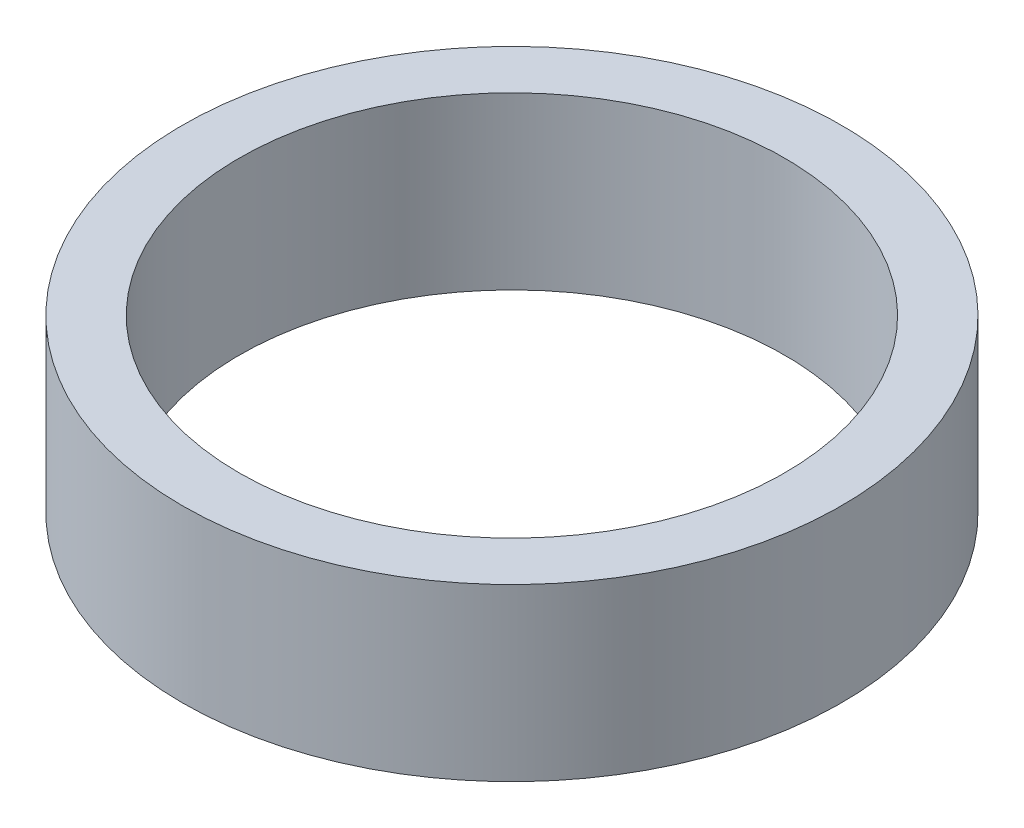
SolidWorks part; units mm, degrees
material "Teak"
ref_plane "Front Plane" through (0, 0, 0) normal (0, 0, 1) x (1, 0, 0)
ref_plane "Top Plane" through (0, 0, 0) normal (0, 1, 0) x (1, 0, 0)
ref_plane "Right Plane" through (0, 0, 0) normal (1, 0, 0) x (0, 0, -1)
sketch "Sketch1" plane through (0, 0, 0) normal (0, 1, 0) x (1, 0, 0)
  circle A0 centre (0, 0) radius 15.975
  circle A1 centre (0, 0) radius 19.305
  dimension "D1" = 38.61
  dimension "D2" = 31.95
extrude "Boss-Extrude1" add sketch "Sketch1" along normal blind 10
